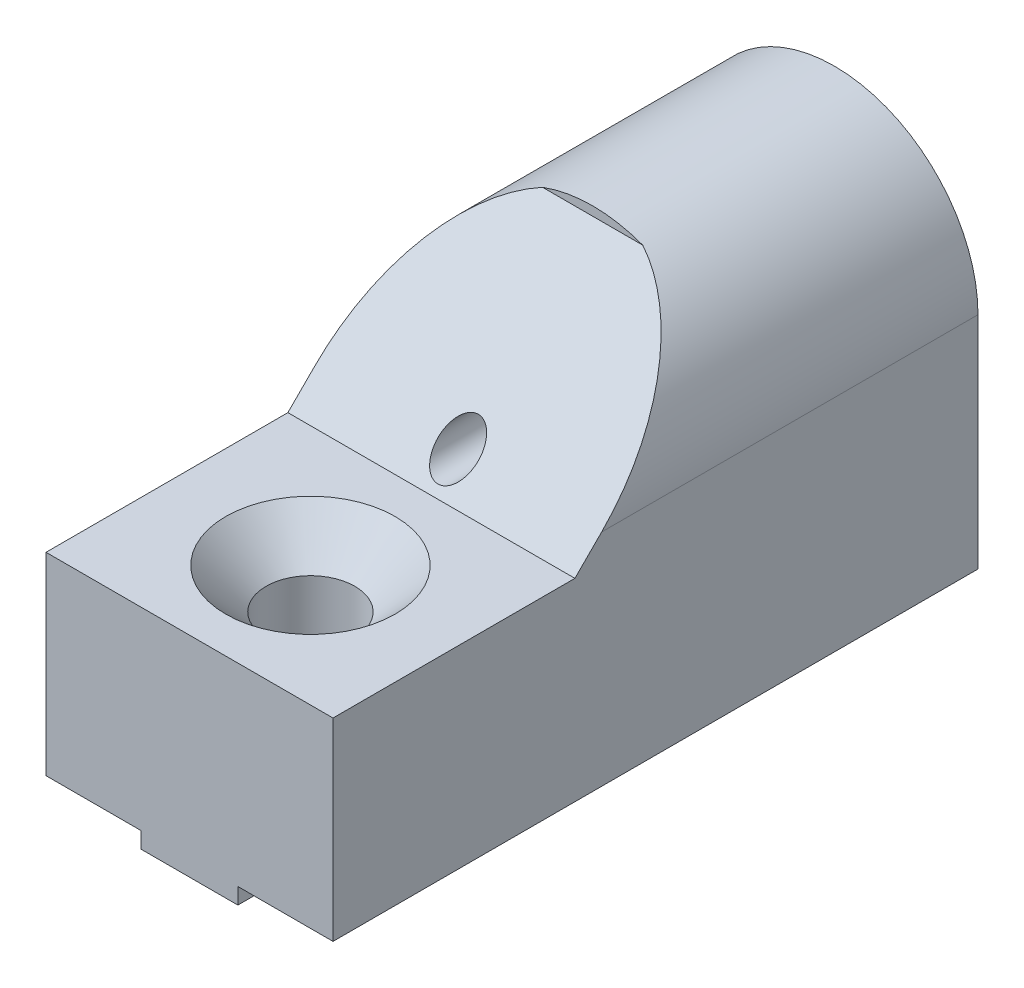
SolidWorks part; units mm, degrees
ref_plane "Top Plane" through (0, 0, 0) normal (0, 0, 1) x (1, 0, 0)
ref_plane "Right Plane" through (0, 0, 0) normal (0, 1, 0) x (1, 0, 0)
ref_plane "Front Plane" through (0, 0, 0) normal (1, 0, 0) x (0, 0, -1)
sketch "Sketch1" plane through (0, 0, 0) normal (0, 0, 1) x (1, 0, 0)
  line L0 (-8.9, -13.66) -> (8.9, -13.66)
  line L1 (-8.9, -13.66) -> (-8.9, 0)
  line L2 (8.9, 0) -> (8.9, -13.66)
  line L3 (0, 0) -> (-8.9, 0) construction
  circle A0 centre (0, 0) radius 1.25
  arc A1 (-8.9, 0) -> (8.9, 0) centre (0, 0) cw
  dimension "D2" = 2.5
  dimension "D1" = 13.66
  dimension "D3" = 17.8
extrude "Boss-Extrude1" add sketch "Sketch1" along normal blind 15
sketch "Sketch2" plane through (0, 0, 15) normal (0, 0, 1) x (1, 0, 0)
  line L0 (8.9, -13.66) -> (8.9, 0) construction
  line L1 (-8.9, -13.66) -> (8.9, -13.66)
  line L2 (-8.9, -13.66) -> (-8.9, -1.66)
  line L3 (-8.9, -1.66) -> (8.9, -1.66)
  line L4 (8.9, -13.66) -> (8.9, -1.66)
  dimension "D1" = 12
extrude "Boss-Extrude2" add sketch "Sketch2" along normal blind 25
chamfer "Chamfer1" distance 10 angle 45 1 edges at (0, -1.66, 15)
sketch "Sketch3" plane through (0, -1.66, 0) normal (0, 1, 0) x (1, 0, 0)
  line L0 (8.9, -32.5) -> (-8.9, -32.5) construction
  line L1 (8.9, -40) -> (8.9, -25) construction
  line L2 (-8.9, -40) -> (-8.9, -25) construction
  circle A0 centre (0, -32.5) radius 2.75
  dimension "D1" = 5.5
extrude "Cut-Extrude1" cut sketch "Sketch3" against normal through all
chamfer "Chamfer2" distance 2.5 angle 45 1 edges at (0, -1.66, 35.25)
sketch "Sketch4" plane through (0, -13.66, 0) normal (0, -1, 0) x (1, 0, 0)
  line L0 (-8.9, 40) -> (8.9, 40) construction
  line L1 (3, 40) -> (-3, 40)
  line L2 (3, 40) -> (3, 0)
  line L3 (3, 0) -> (-3, 0)
  line L4 (-3, 40) -> (-3, 0)
  line L5 (-8.9, 0) -> (8.9, 0) construction
  circle A0 centre (0, 32.5) radius 2.75
  circle A1 centre (0, 32.5) radius 2.75 construction
  point P8 (0, 40)
  dimension "D1" = 6
extrude "Boss-Extrude3" add sketch "Sketch4" along normal blind 1
